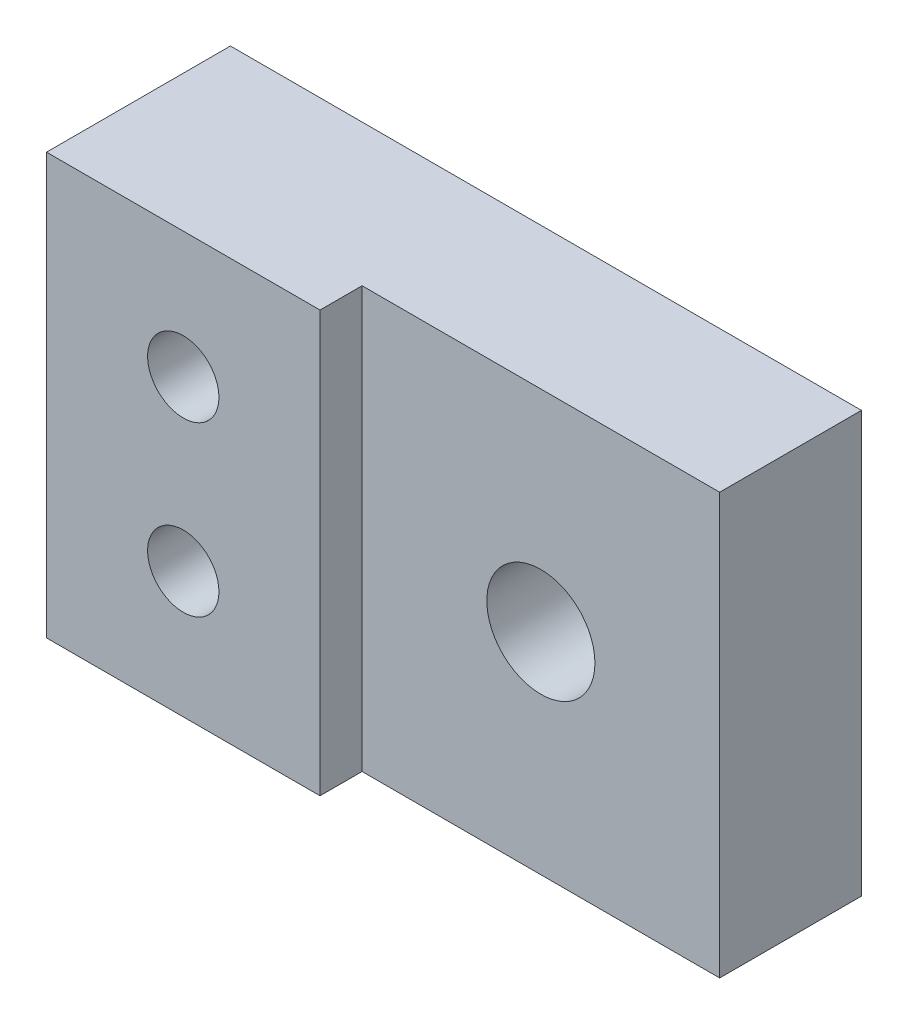
SolidWorks part; units mm, degrees
material "6061-T6 (SS)"
ref_plane "Front Plane" through (0, 0, 0) normal (0, 0, 1) x (1, 0, 0)
ref_plane "Top Plane" through (0, 0, 0) normal (0, 1, 0) x (1, 0, 0)
ref_plane "Right Plane" through (0, 0, 0) normal (1, 0, 0) x (0, 0, -1)
sketch "Sketch1" plane through (0, 0, 0) normal (0, 0, 1) x (1, 0, 0)
  line L0 (7.4474, 16.3386) -> (7.4474, 10.4838) construction
  line L1 (7.4474, 6.1785) -> (7.4474, 0.7112) construction
  line L2 (-0.8076, 26.1112) -> (37.2924, 26.1112)
  line L3 (15.7024, 26.1112) -> (15.7024, 0.7112)
  line L4 (-0.8076, 0.7112) -> (37.2924, 0.7112) construction
  line L5 (37.2924, 0.7112) -> (37.2924, 39.0516) construction
  line L6 (7.4474, 20.6439) -> (7.4474, 26.1112) construction
  line L7 (-0.8076, 0.7112) -> (-0.8076, 36.2712) construction
  line L8 (-0.8076, 0.7112) -> (37.2924, 0.7112)
  line L9 (37.2924, 0.7112) -> (37.2924, 26.1112)
  line L11 (-0.8076, 26.1112) -> (-0.8076, 0.7112)
  line L16 (15.7024, 26.1112) -> (15.7024, 0.7112) construction
  circle A3 centre (26.4974, 13.4112) radius 3.2639
  circle A4 centre (7.4474, 8.3312) radius 2.1526
  circle A5 centre (7.4474, 18.4912) radius 2.1526
  point P20 (7.4474, 13.4112)
  dimension "D2" = 4.3053
  dimension "D3" = 12.7
  dimension "D6" = 5.8547
  dimension "D8" = 6.5278
  dimension "D5" = 5.4673
  dimension "D1" = 5.4673
  dimension "D4" = 8.255
  dimension "D7" = 10.795
  dimension "D10" = 7.62
  dimension "D11" = 7.62
  dimension "D12" = 25.4
extrude "Boss-Extrude1" add sketch "Sketch1" along normal blind 11.0998 contours L2 L11 L8 L3 A5 A4 region at (7.4474, 13.4112, 0)
extrude "Boss-Extrude2" add sketch "Sketch1<3>" along normal blind 8.5598 contours L8 L9 L2 L3 A3 region at (26.4974, 25.7778, 0)
sketch "Sketch1<3>" plane through (0, 0, 0) normal (0, 0, 1) x (1, 0, 0) same geometry as "Sketch1"
